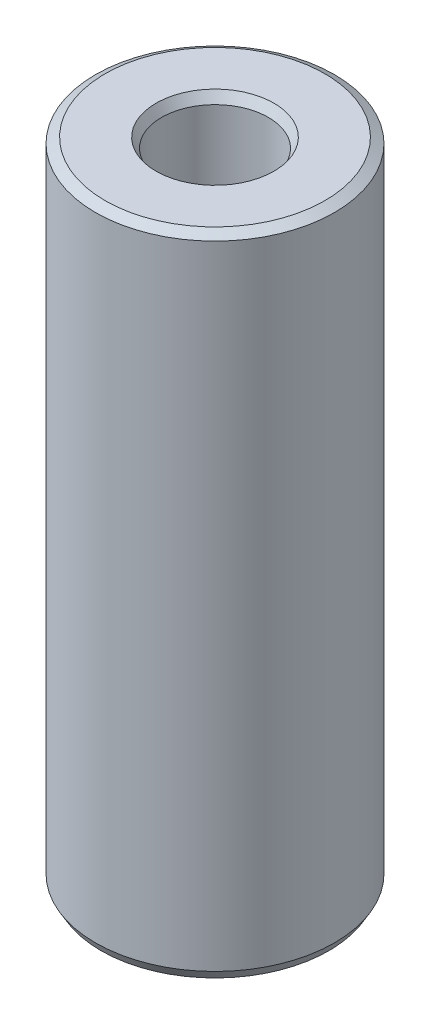
SolidWorks part; units mm, degrees
ref_plane "Front Plane" through (0, 0, 0) normal (0, 0, 1) x (1, 0, 0)
ref_plane "Top Plane" through (0, 0, 0) normal (0, 1, 0) x (1, 0, 0)
ref_plane "Right Plane" through (0, 0, 0) normal (1, 0, 0) x (0, 0, -1)
sketch "Sketch1" plane through (0, 0, 0) normal (0, 1, 0) x (1, 0, 0)
  circle A0 centre (0, 0) radius 7.5
  dimension "SLEEVE_OD" = 15
extrude "Boss-Extrude1" add sketch "Sketch1" along normal blind 40.6447
sketch "Sketch2" plane through (0, 0, 0) normal (0, 1, 0) x (1, 0, 0)
  circle A0 centre (0, 0) radius 3.354
  dimension "BORE_D" = 6.7081
extrude "Cut-Extrude1" cut sketch "Sketch2" along normal through all
chamfer "Chamfer1" distance 0.3467 angle 60 4 edges at (0, 40.6447, 3.354) (0, 0, 3.354) (0, 0, 7.5) (0, 40.6447, 7.5) first distance on face at (0, 40.6447, 3.354) first distance on face at (0, 0, 3.354) first distance on face at (0, 40.6447, 7.5)
